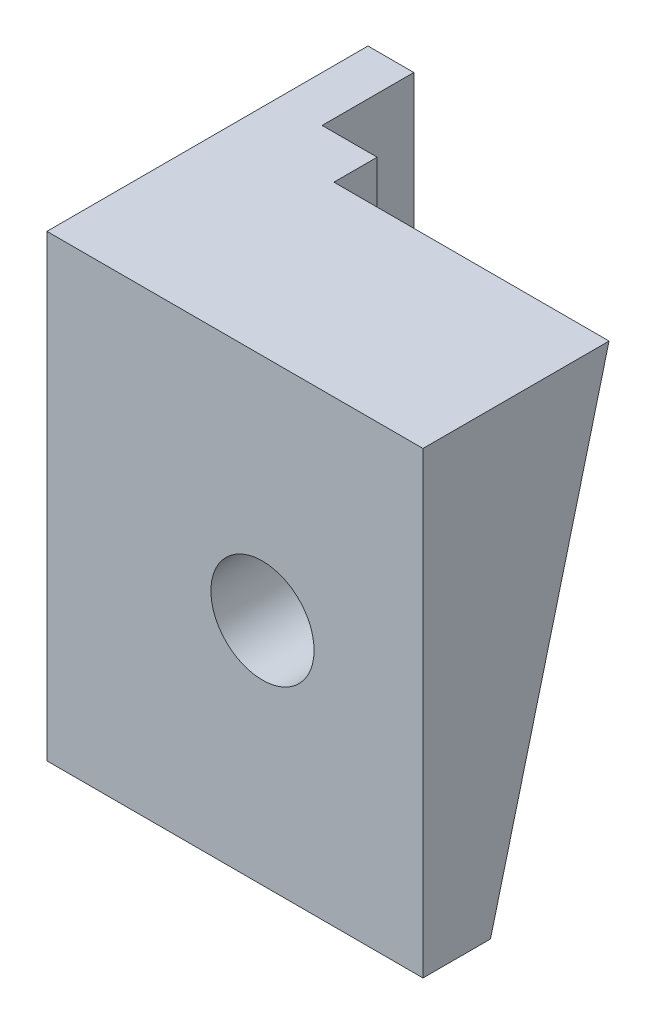
SolidWorks part; units mm, degrees
ref_plane "Front Plane" through (0, 0, 0) normal (0, 0, 1) x (1, 0, 0)
ref_plane "Top Plane" through (0, 0, 0) normal (0, 1, 0) x (1, 0, 0)
ref_plane "Right Plane" through (0, 0, 0) normal (1, 0, 0) x (0, 0, -1)
sketch "Sketch2" plane through (0, 0, 0) normal (0, 0, 1) x (1, 0, 0)
  line L1 (0, 0) -> (1, 0)
  line L2 (0, 0) -> (0, 10)
  line L3 (0, 10) -> (1, 10)
  line L4 (1, 0) -> (1, 10)
  line L5 (1, 0) -> (2.2, 0)
  line L6 (1, 0) -> (1, 10)
  line L7 (1, 10) -> (2.2, 10)
  line L8 (2.2, 0) -> (2.2, 10)
  dimension "D1" = 10
  dimension "D2" = 1
  dimension "D3" = 1.2
extrude "Boss-Extrude1" add sketch "Sketch2" along normal blind 5 contours L5 L8 L7 L4 | L1 L4 L3 L2 region at (0.5, 5, 0) region at (1.6, 5, 0)
extrude "Boss-Extrude2" add sketch "Sketch2<3>" against normal blind 2 contours L1 L4 L3 L2 region at (0.5, 5, 0)
sketch "Sketch2<3>" plane through (0, 0, 0) normal (0, 0, 1) x (1, 0, 0) same geometry as "Sketch2"
sketch "Sketch3" plane through (2.2, 0, 0) normal (1, 0, 0) x (0, 0, -1)
  line L0 (-3.529, 0) -> (-0.9429, 10)
  line L1 (-5, 0) -> (0, 0) construction
  line L2 (-5, 10) -> (0, 10) construction
  line M3 (0, 10) -> (-5, 10)
  line M4 (-5, 10) -> (-5, 0)
  line M5 (-5, 0) -> (0, 0)
  dimension "D1" = 1.471
  dimension "D2" = 75.5
extrude "Boss-Extrude3" add sketch "Sketch3" along normal blind 6 contours L0 M5 M3 M4 region at (2.2, 5.7797, 3.5171)
sketch "Sketch4" plane through (0, 0, 5) normal (0, 0, 1) x (1, 0, 0)
  line L0 (0, 10) -> (8.2, 10) construction
  line L2 (8.2, 10) -> (8.2, 0) construction
  circle A0 centre (4.7, 5) radius 1.125
  point P10 (8.2, 4.7977)
  dimension "D1" = 2.25
  dimension "D2" = 5
  dimension "D3" = 3.5
extrude "Cut-Extrude1" cut sketch "Sketch4" against normal blind 6
